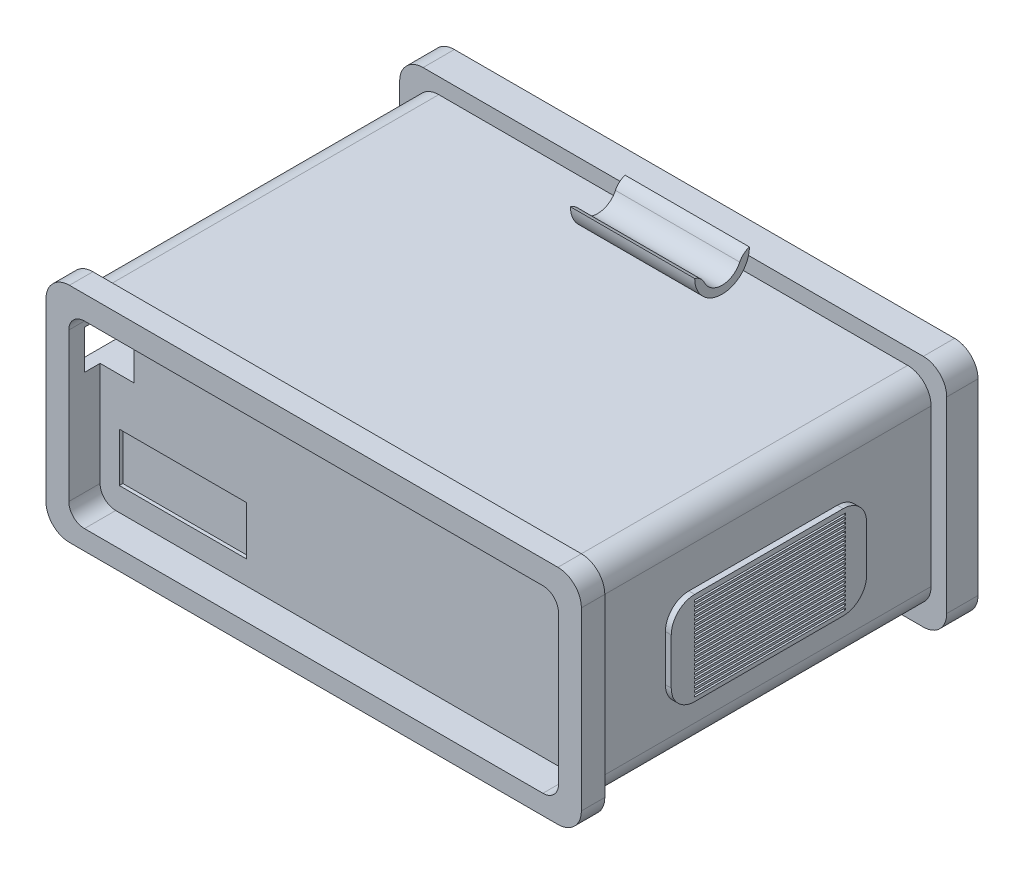
SolidWorks part; units mm, degrees
material "Custom Plastic"
ref_plane "Front Plane" through (0, 0, 0) normal (0, 0, 1) x (1, 0, 0)
ref_plane "Top Plane" through (0, 0, 0) normal (0, 1, 0) x (1, 0, 0)
ref_plane "Right Plane" through (0, 0, 0) normal (1, 0, 0) x (0, 0, -1)
sketch "Sketch1" plane through (0, 0, 0) normal (0, 0, 1) x (1, 0, 0)
  line L1 (-353.5354, 43.9394) -> (346.4646, 43.9394)
  line L2 (-353.5354, 43.9394) -> (-353.5354, -256.0606)
  line L3 (-353.5354, -256.0606) -> (346.4646, -256.0606)
  line L4 (346.4646, 43.9394) -> (346.4646, -256.0606)
  dimension "D1" = 700
  dimension "D2" = 300
extrude "Boss-Extrude1" add sketch "Sketch1" along normal blind 500
sketch "Sketch3" plane through (0, 43.9394, 0) normal (0, 1, 0) x (1, 0, 0)
  line L0 (346.4646, -500) -> (346.4646, 0) construction
  line L1 (-353.5354, -40) -> (346.4646, -40)
  line L2 (-353.5354, -40) -> (-353.5354, -470)
  line L3 (-353.5354, -470) -> (346.4646, -470)
  line L4 (346.4646, -40) -> (346.4646, -470)
  line L5 (346.4646, 0) -> (-353.5354, 0) construction
  line L6 (-353.5354, -500) -> (-353.5354, 0) construction
  line L7 (346.4646, -500) -> (-353.5354, -500) construction
  dimension "D1" = 0
  dimension "D2" = 40
  dimension "D3" = 0
  dimension "D4" = 30
extrude "Cut-Extrude1" cut sketch "Sketch3" against normal blind 20
sketch "Sketch4" plane through (-353.5354, 0, 0) normal (-1, 0, 0) x (0, 0, 1)
  line L0 (500, -256.0606) -> (0, -256.0606) construction
  line L1 (40, 23.9394) -> (470, 23.9394)
  line L2 (40, 23.9394) -> (40, -256.0606)
  line L3 (40, -256.0606) -> (470, -256.0606)
  line L4 (470, 23.9394) -> (470, -256.0606)
extrude "Cut-Extrude2" cut sketch "Sketch4" against normal blind 20
sketch "Sketch5" plane through (0, -256.0606, 0) normal (0, -1, 0) x (-1, 0, 0)
  line L1 (333.5354, -470) -> (-346.4646, -470)
  line L2 (333.5354, -470) -> (333.5354, -40)
  line L3 (333.5354, -40) -> (-346.4646, -40)
  line L4 (-346.4646, -470) -> (-346.4646, -40)
extrude "Cut-Extrude3" cut sketch "Sketch5" against normal blind 20
sketch "Sketch6" plane through (346.4646, 0, 0) normal (1, 0, 0) x (0, 0, -1)
  line L1 (-470, 23.9394) -> (-40, 23.9394)
  line L2 (-470, 23.9394) -> (-470, -236.0606)
  line L3 (-470, -236.0606) -> (-40, -236.0606)
  line L4 (-40, 23.9394) -> (-40, -236.0606)
extrude "Cut-Extrude4" cut sketch "Sketch6" against normal blind 20
sketch "Sketch7" plane through (346.4646, 0, 0) normal (1, 0, 0) x (0, 0, -1)
  line L1 (-500, 43.9394) -> (-470, 43.9394)
  line L2 (-500, 43.9394) -> (-500, -256.0606)
  line L3 (-500, -256.0606) -> (-470, -256.0606)
  line L4 (-470, 43.9394) -> (-470, -256.0606)
extrude "Cut-Extrude5" cut sketch "Sketch7" against normal blind 7.5
sketch "Sketch8" plane through (0, 43.9394, 0) normal (0, 1, 0) x (1, 0, 0)
  line L1 (-353.5354, -470) -> (338.9646, -470)
  line L2 (-353.5354, -470) -> (-353.5354, -500)
  line L3 (-353.5354, -500) -> (338.9646, -500)
  line L4 (338.9646, -470) -> (338.9646, -500)
extrude "Cut-Extrude6" cut sketch "Sketch8" against normal blind 7.5
sketch "Sketch9" plane through (-353.5354, 0, 0) normal (-1, 0, 0) x (0, 0, 1)
  line L1 (470, 36.4394) -> (500, 36.4394)
  line L2 (470, 36.4394) -> (470, -256.0606)
  line L3 (470, -256.0606) -> (500, -256.0606)
  line L4 (500, 36.4394) -> (500, -256.0606)
extrude "Cut-Extrude7" cut sketch "Sketch9" against normal blind 7.5
sketch "Sketch10" plane through (0, -256.0606, 0) normal (0, -1, 0) x (-1, 0, 0)
  line L1 (346.0354, -500) -> (-338.9646, -500)
  line L2 (346.0354, -500) -> (346.0354, -470)
  line L3 (346.0354, -470) -> (-338.9646, -470)
  line L4 (-338.9646, -500) -> (-338.9646, -470)
extrude "Cut-Extrude8" cut sketch "Sketch10" against normal blind 7.5
fillet "Fillet1" radius 30 12 edges at (-346.0354, -248.5606, 485) (-346.0354, 36.4394, 485) (338.9646, -248.5606, 485) (338.9646, 36.4394, 485) (346.4646, -256.0606, 20) (346.4646, 43.9394, 20) (-353.5354, 43.9394, 20) (-353.5354, -256.0606, 20) (326.4646, 23.9394, 255) (326.4646, -236.0606, 255) (-333.5354, 23.9394, 255) (-333.5354, -236.0606, 255)
sketch "Sketch11" plane through (326.4646, 0, 0) normal (1, 0, 0) x (0, 0, -1)
  line L0 (-40, -6.0606) -> (-470, -6.0606) construction
  line L1 (-380, -56.0606) -> (-130, -56.0606)
  line L2 (-380, -56.0606) -> (-380, -174.9296)
  line L3 (-380, -174.9296) -> (-130, -174.9296)
  line L4 (-130, -56.0606) -> (-130, -174.9296)
  line L5 (-375, -61.0606) -> (-135, -61.0606)
  line L6 (-375, -61.0606) -> (-375, -169.9296)
  line L7 (-375, -169.9296) -> (-135, -169.9296)
  line L8 (-135, -61.0606) -> (-135, -169.9296)
  line L10 (-470, -6.0606) -> (-40, -6.0606)
  point P10 (-255, -6.0606)
  point P11 (-255, -56.0606)
  dimension "D1" = 5
  dimension "D2" = 5
  dimension "D3" = 5
  dimension "D4" = 5
  dimension "D5" = 50
  dimension "D7" = 250
extrude "Boss-Extrude2" add sketch "Sketch11" along normal blind 7.5 contours L2 L3 L4 L1
fillet "Fillet2" radius 30 4 edges at (330.2146, -56.0606, 380) (330.2146, -174.9296, 380) (330.2146, -174.9296, 130) (330.2146, -56.0606, 130)
sketch "Sketch12" plane through (333.9646, 0, 0) normal (1, 0, 0) x (0, 0, -1)
  line L0 (-255, -56.0606) -> (-255, -174.9296)
  line L1 (-350, -62.3474) -> (-157.0383, -62.3474)
  line L2 (-350, -62.3474) -> (-350, -64.8474)
  line L3 (-350, -64.8474) -> (-157.0383, -64.8474)
  line L4 (-157.0383, -62.3474) -> (-157.0383, -64.8474)
  line L5 (-350, -56.0606) -> (-160, -56.0606) construction
  line L6 (-350, -174.9296) -> (-160, -174.9296) construction
  line L7 (-350, -67.3474) -> (-157.0383, -67.3474)
  line L8 (-350, -69.8474) -> (-157.0383, -69.8474)
  line L9 (-350, -67.3474) -> (-350, -69.8474)
  line L10 (-157.0383, -67.3474) -> (-157.0383, -69.8474)
  line L11 (-350, -72.3474) -> (-157.0383, -72.3474)
  line L12 (-350, -74.8474) -> (-157.0383, -74.8474)
  line L13 (-350, -72.3474) -> (-350, -74.8474)
  line L14 (-157.0383, -72.3474) -> (-157.0383, -74.8474)
  line L15 (-350, -77.3474) -> (-157.0383, -77.3474)
  line L16 (-350, -79.8474) -> (-157.0383, -79.8474)
  line L17 (-350, -77.3474) -> (-350, -79.8474)
  line L18 (-157.0383, -77.3474) -> (-157.0383, -79.8474)
  line L19 (-350, -82.3474) -> (-157.0383, -82.3474)
  line L20 (-350, -84.8474) -> (-157.0383, -84.8474)
  line L21 (-350, -82.3474) -> (-350, -84.8474)
  line L22 (-157.0383, -82.3474) -> (-157.0383, -84.8474)
  line L23 (-350, -87.3474) -> (-157.0383, -87.3474)
  line L24 (-350, -89.8474) -> (-157.0383, -89.8474)
  line L25 (-350, -87.3474) -> (-350, -89.8474)
  line L26 (-157.0383, -87.3474) -> (-157.0383, -89.8474)
  line L27 (-350, -92.3474) -> (-157.0383, -92.3474)
  line L28 (-350, -94.8474) -> (-157.0383, -94.8474)
  line L29 (-350, -92.3474) -> (-350, -94.8474)
  line L30 (-157.0383, -92.3474) -> (-157.0383, -94.8474)
  line L31 (-350, -97.3474) -> (-157.0383, -97.3474)
  line L32 (-350, -99.8474) -> (-157.0383, -99.8474)
  line L33 (-350, -97.3474) -> (-350, -99.8474)
  line L34 (-157.0383, -97.3474) -> (-157.0383, -99.8474)
  line L35 (-350, -102.3474) -> (-157.0383, -102.3474)
  line L36 (-350, -104.8474) -> (-157.0383, -104.8474)
  line L37 (-350, -102.3474) -> (-350, -104.8474)
  line L38 (-157.0383, -102.3474) -> (-157.0383, -104.8474)
  line L39 (-350, -107.3474) -> (-157.0383, -107.3474)
  line L40 (-350, -109.8474) -> (-157.0383, -109.8474)
  line L41 (-350, -107.3474) -> (-350, -109.8474)
  line L42 (-157.0383, -107.3474) -> (-157.0383, -109.8474)
  line L43 (-350, -112.3474) -> (-157.0383, -112.3474)
  line L44 (-350, -114.8474) -> (-157.0383, -114.8474)
  line L45 (-350, -112.3474) -> (-350, -114.8474)
  line L46 (-157.0383, -112.3474) -> (-157.0383, -114.8474)
  line L47 (-350, -117.3474) -> (-157.0383, -117.3474)
  line L48 (-350, -119.8474) -> (-157.0383, -119.8474)
  line L49 (-350, -117.3474) -> (-350, -119.8474)
  line L50 (-157.0383, -117.3474) -> (-157.0383, -119.8474)
  line L51 (-350, -122.3474) -> (-157.0383, -122.3474)
  line L52 (-350, -124.8474) -> (-157.0383, -124.8474)
  line L53 (-350, -122.3474) -> (-350, -124.8474)
  line L54 (-157.0383, -122.3474) -> (-157.0383, -124.8474)
  line L55 (-350, -127.3474) -> (-157.0383, -127.3474)
  line L56 (-350, -129.8474) -> (-157.0383, -129.8474)
  line L57 (-350, -127.3474) -> (-350, -129.8474)
  line L58 (-157.0383, -127.3474) -> (-157.0383, -129.8474)
  line L59 (-350, -132.3474) -> (-157.0383, -132.3474)
  line L60 (-350, -134.8474) -> (-157.0383, -134.8474)
  line L61 (-350, -132.3474) -> (-350, -134.8474)
  line L62 (-157.0383, -132.3474) -> (-157.0383, -134.8474)
  line L63 (-350, -137.3474) -> (-157.0383, -137.3474)
  line L64 (-350, -139.8474) -> (-157.0383, -139.8474)
  line L65 (-350, -137.3474) -> (-350, -139.8474)
  line L66 (-157.0383, -137.3474) -> (-157.0383, -139.8474)
  line L67 (-350, -142.3474) -> (-157.0383, -142.3474)
  line L68 (-350, -144.8474) -> (-157.0383, -144.8474)
  line L69 (-350, -142.3474) -> (-350, -144.8474)
  line L70 (-157.0383, -142.3474) -> (-157.0383, -144.8474)
  line L71 (-350, -147.3474) -> (-157.0383, -147.3474)
  line L72 (-350, -149.8474) -> (-157.0383, -149.8474)
  line L73 (-350, -147.3474) -> (-350, -149.8474)
  line L74 (-157.0383, -147.3474) -> (-157.0383, -149.8474)
  line L75 (-350, -152.3474) -> (-157.0383, -152.3474)
  line L76 (-350, -154.8474) -> (-157.0383, -154.8474)
  line L77 (-350, -152.3474) -> (-350, -154.8474)
  line L78 (-157.0383, -152.3474) -> (-157.0383, -154.8474)
  line L79 (-350, -157.3474) -> (-157.0383, -157.3474)
  line L80 (-350, -159.8474) -> (-157.0383, -159.8474)
  line L81 (-350, -157.3474) -> (-350, -159.8474)
  line L82 (-157.0383, -157.3474) -> (-157.0383, -159.8474)
  line L83 (-350, -162.3474) -> (-157.0383, -162.3474)
  line L84 (-350, -164.8474) -> (-157.0383, -164.8474)
  line L85 (-350, -162.3474) -> (-350, -164.8474)
  line L86 (-157.0383, -162.3474) -> (-157.0383, -164.8474)
  line L87 (-350, -167.3474) -> (-157.0383, -167.3474)
  line L88 (-350, -169.8474) -> (-157.0383, -169.8474)
  line L89 (-350, -167.3474) -> (-350, -169.8474)
  line L90 (-157.0383, -167.3474) -> (-157.0383, -169.8474)
  dimension "D1" = 2.5
  dimension "D2" = 22
extrude "Cut-Extrude9" cut sketch "Sketch12" against normal blind 15.5 contours L7 L10 L8 L9 | L31 L34 L32 L33 | L1 L4 L3 L2 | L11 L14 L12 L13 | L15 L18 L16 L17 | L19 L22 L20 L21 | L23 L26 L24 L25 | L27 L30 L28 L29 | L35 L38 L36 L37 | L39 L42 L40 L41 | L43 L46 L44 L45 | L47 L50 L48 L49 | L51 L54 L52 L53 | L55 L58 L56 L57 | L59 L62 L60 L61 | L63 L66 L64 L65 | L67 L70 L68 L69 | L71 L74 L72 L73 | L75 L78 L76 L77 | L79 L82 L80 L81 | L83 L86 L84 L85 | L87 L90 L88 L89
sketch "Sketch13" plane through (0, 0, 0) normal (0, 0, -1) x (-1, 0, 0)
  line L1 (-307.2513, -30.944) -> (-47.2513, -30.944)
  line L3 (-307.2513, -50.944) -> (-47.2513, -50.944)
  arc A0 (-47.2513, -30.944) -> (-47.2513, -50.944) centre (-47.2513, -40.944) cw
  arc A1 (-307.2513, -30.944) -> (-307.2513, -50.944) centre (-307.2513, -40.944) ccw
  dimension "D1" = 260
  dimension "D2" = 20
extrude "Cut-Extrude10" cut sketch "Sketch13" against normal blind 15
sketch "Sketch14" plane through (0, 0, 500) normal (0, 0, 1) x (1, 0, 0)
  line L0 (-316.0354, 36.4394) -> (308.9646, 36.4394) construction
  line L1 (-316.8328, 6.4394) -> (309.7621, 6.4394)
  line L2 (-316.8328, 6.4394) -> (-316.8328, -223.5606)
  line L3 (-316.8328, -223.5606) -> (309.7621, -223.5606)
  line L4 (309.7621, 6.4394) -> (309.7621, -223.5606)
  point P6 (-3.5354, 36.4394)
  point P7 (-3.5354, 6.4394)
  dimension "D1" = 626.595
  dimension "D2" = 30
  dimension "D3" = 230
extrude "Cut-Extrude11" cut sketch "Sketch14" against normal blind 40
fillet "Fillet3" radius 20 4 edges at (-316.8328, -223.5606, 480) (-316.8328, 6.4394, 480) (309.7621, -223.5606, 480) (309.7621, 6.4394, 480)
sketch "Sketch15" plane through (0, 0, 460) normal (0, 0, 1) x (1, 0, 0)
  line L0 (-296.8328, -223.5606) -> (289.7621, -223.5606) construction
  line L1 (-292.2753, -131.0606) -> (-129.7753, -131.0606)
  line L2 (-292.2753, -131.0606) -> (-292.2753, -193.5606)
  line L3 (-292.2753, -193.5606) -> (-129.7753, -193.5606)
  line L4 (-129.7753, -131.0606) -> (-129.7753, -193.5606)
  dimension "D1" = 162.5
  dimension "D2" = 62.5
  dimension "D3" = 30
extrude "Cut-Extrude12" cut sketch "Sketch15" against normal blind 4.5
sketch "Sketch16" plane through (-353.5354, 0, 0) normal (-1, 0, 0) x (0, 0, 1)
  line L0 (45, 58.9394) -> (55, 58.9394)
  line L1 (105, 58.9394) -> (115, 58.9394)
  line L2 (0, 43.9394) -> (0, 13.9394) construction
  line L3 (40, 23.9394) -> (470, 23.9394) construction
  arc A0 (45, 58.9394) -> (115, 58.9394) centre (80, 58.9394) ccw
  arc A1 (55, 58.9394) -> (105, 58.9394) centre (80, 58.9394) ccw
  dimension "D1" = 80
  dimension "D2" = 35
extrude "Boss-Extrude3" add sketch "Sketch16" against normal blind 452.5 separate body
sketch "Sketch17" plane through (-353.5354, 0, 0) normal (-1, 0, 0) x (0, 0, 1)
  circle A0 centre (80, 58.9394) radius 35
extrude "Cut-Extrude13" cut sketch "Sketch17" against normal blind 293.5
fillet "Fillet4" radius 20 2 edges at (19.4646, 58.9394, 55) (19.4646, 58.9394, 105)
sketch "Sketch18" plane through (0, 0, 0) normal (0, 0, -1) x (-1, 0, 0)
  line L0 (353.5354, 13.9394) -> (353.5354, -226.0606) construction
  line L1 (353.5354, -20.4689) -> (273.5354, -20.4689)
  line L2 (353.5354, -20.4689) -> (353.5354, -70.4689)
  line L3 (353.5354, -70.4689) -> (273.5354, -70.4689)
  line L4 (273.5354, -20.4689) -> (273.5354, -70.4689)
  dimension "D1" = 50
  dimension "D2" = 80
extrude "Cut-Extrude14" cut sketch "Sketch18" against normal blind 480
